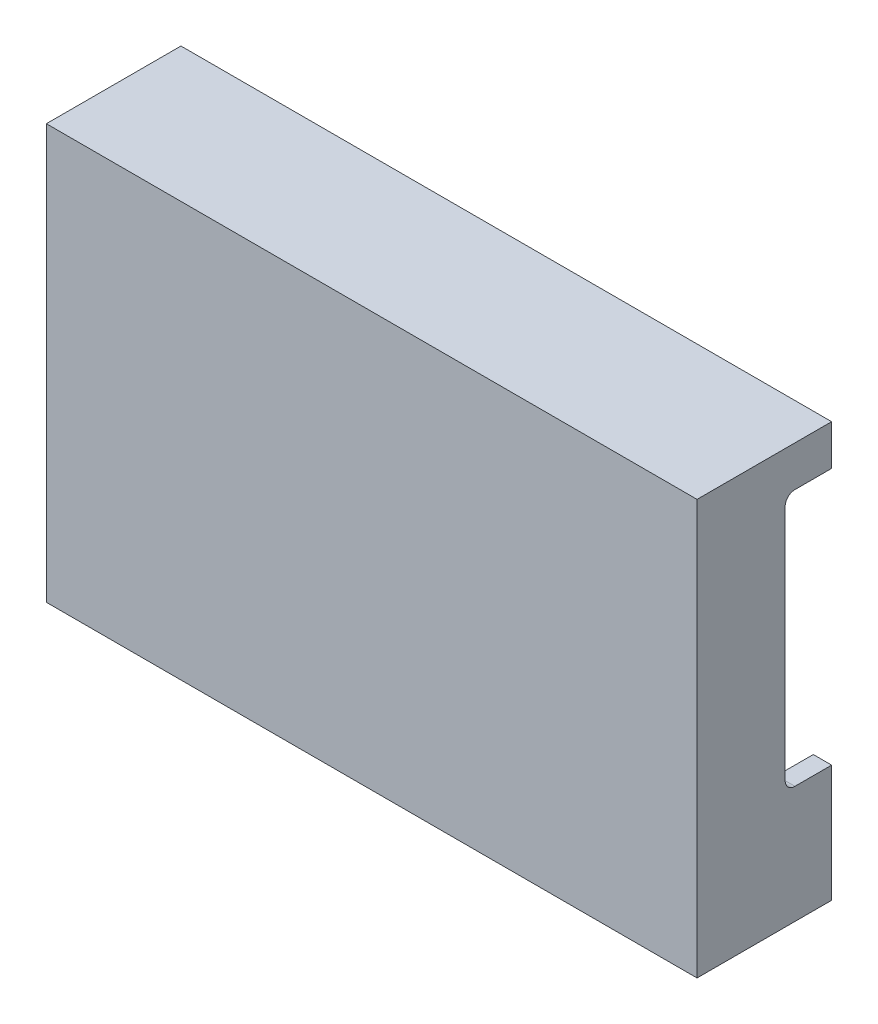
SolidWorks part; units mm, degrees
ref_plane "Спереди" through (0, 0, 0) normal (0, 0, 1) x (1, 0, 0)
ref_plane "Сверху" through (0, 0, 0) normal (0, 1, 0) x (1, 0, 0)
ref_plane "Справа" through (0, 0, 0) normal (1, 0, 0) x (0, 0, -1)
sketch "Эскиз1" plane through (0, 0, 0) normal (0, 0, 1) x (1, 0, 0)
  line L0 (48.984, 29.68) -> (49.984, 29.68)
  line L1 (0, 0) -> (49.784, 0) construction
  line L2 (0, 0) -> (0, 30.48) construction
  line L3 (0, 30.48) -> (49.784, 30.48) construction
  line L4 (49.784, 0) -> (49.784, 30.48) construction
  line L5 (-0.2, -0.2) -> (49.984, -0.2)
  line L6 (-0.2, -0.2) -> (-0.2, 30.68)
  line L7 (-0.2, 30.68) -> (49.984, 30.68)
  line L8 (49.984, -0.2) -> (49.984, 30.68)
  line L9 (0.8, 0.8) -> (48.984, 0.8)
  line L10 (0.8, 0.8) -> (0.8, 29.68)
  line L11 (0.8, 29.68) -> (48.984, 29.68)
  line L12 (48.984, 0.8) -> (48.984, 29.68)
  line L13 (48.984, 6) -> (49.984, 6)
  line L15 (-1.7, -1.7) -> (51.484, -1.7)
  line L16 (-1.7, -1.7) -> (-1.7, 32.18)
  line L17 (-1.7, 32.18) -> (51.484, 32.18)
  line L18 (51.484, -1.7) -> (51.484, 32.18)
  dimension "D1" = 30.48
  dimension "D2" = 49.784
  dimension "D3" = 0.8
  dimension "D4" = 0.8
  dimension "D5" = 0.8
  dimension "D6" = 0.8
  dimension "D7" = 6
  dimension "D8" = 0.2
  dimension "D9" = 0.2
  dimension "D10" = 0.2
  dimension "D11" = 0.2
  dimension "D12" = 1.5
  dimension "D13" = 1.5
  dimension "D14" = 1.5
  dimension "D15" = 1.5
extrude "Бобышка-Вытянуть1" add sketch "Эскиз1" against normal blind 2 contours L9 L12 L11 L10 | L12 L13 L8 L0 region at (24.892, 15.24, 0) region at (49.484, 17.84, 0)
extrude "Бобышка-Вытянуть2" add sketch "Эскиз1<6>" against normal blind 11.4 contours L13 L12 L9 L10 L11 L0 L8 L7 L6 L5 region at (24.892, 30.2692, 0)
sketch "Эскиз1<6>" plane through (0, 0, 0) normal (0, 0, 1) x (1, 0, 0) same geometry as "Эскиз1"
extrude "Бобышка-Вытянуть3" add sketch "Эскиз1<7>" against normal blind 11 contours L15 L18 L17 L16 L8 L5 L6 L7 region at (-1.0694, 15.24, 0)
sketch "Эскиз1<7>" plane through (0, 0, 0) normal (0, 0, 1) x (1, 0, 0) same geometry as "Эскиз1"
sketch "Эскиз2" plane through (49.984, 0, 0) normal (-1, 0, 0) x (0, 0, 1)
  line L0 (-11, 6) -> (-11, 29.68) construction
  line L1 (-11, 28.87) -> (-7.2, 28.87)
  line L2 (-11, 28.87) -> (-11, 7.87)
  line L3 (-11, 7.87) -> (-7.2, 7.87)
  line L4 (-7.2, 28.87) -> (-7.2, 7.87)
  line L5 (-11.4, 6) -> (-2, 6) construction
  point P8 (-11, 18.37)
  dimension "D1" = 21
  dimension "D2" = 12.37
  dimension "D3" = 3.8
extrude "Вырез-Вытянуть1" cut sketch "Эскиз2" against normal through all
sketch "Эскиз3" plane through (0.8, 0, 0) normal (1, 0, 0) x (0, 0, -1)
  line L0 (11.4, 0.8) -> (11.4, 29.68) construction
  line L1 (11.4, 29.5) -> (6.4, 29.5)
  line L2 (11.4, 29.5) -> (11.4, 19.5)
  line L3 (11.4, 19.5) -> (6.4, 19.5)
  line L4 (6.4, 29.5) -> (6.4, 19.5)
  line L6 (11.4, 14.75) -> (2.4, 14.75)
  line L7 (11.4, 14.75) -> (11.4, 1.75)
  line L8 (11.4, 1.75) -> (2.4, 1.75)
  line L9 (2.4, 14.75) -> (2.4, 1.75)
  line L10 (11.4, -0.2) -> (11, -0.2) construction
  point P10 (6.4, 24.5)
  point P15 (2.4, 8.25)
  dimension "D1" = 24.7
  dimension "D2" = 10
  dimension "D3" = 5
  dimension "D4" = 8.45
  dimension "D5" = 13
  dimension "D6" = 9
extrude "Вырез-Вытянуть2" cut sketch "Эскиз3" against normal through all
fillet "Скругление1" radius 0.8 6 edges at (50.734, 7.87, -7.2) (50.734, 28.87, -7.2) (-0.45, 19.5, -6.4) (-0.45, 29.5, -6.4) (-0.45, 1.75, -2.4) (-0.45, 14.75, -2.4)
chamfer "Фаска1" distance 0.4 angle 45 7 edges at (-0.2, 0.775, -11.4) (24.892, -0.2, -11.4) (49.984, 2.9, -11.4) (49.984, 30.18, -11.4) (24.892, 30.68, -11.4) (-0.2, 30.09, -11.4) (-0.2, 17.125, -11.4)
sketch "Эскиз4" plane through (0, 0, -2) normal (0, 0, -1) x (-1, 0, 0)
  line L0 (0.2, -0.2) -> (0.2, 1.75) construction
  line L1 (0.2, -0.2) -> (-49.984, -0.2) construction
  line L2 (-0.8, 29.68) -> (-49.984, 29.68) construction
  line L3 (-35.3, 29.68) -> (-33.3, 29.68)
  line L4 (-35.3, 29.68) -> (-35.3, 21.68)
  line L5 (-35.3, 21.68) -> (-33.3, 21.68)
  line L6 (-33.3, 29.68) -> (-33.3, 21.68)
  circle A0 centre (-11.8, 2.8) radius 2
  circle A1 centre (-27.6, 27.6) radius 2
  circle A2 centre (-40.9, 27.6) radius 2
  point P16 (-34.3, 21.68)
  line M6 (-0.8, 29.68) -> (-49.984, 29.68)
  dimension "D3" = 4
  dimension "D6" = 4
  dimension "D8" = 4
  dimension "D1" = 12
  dimension "D2" = 3
  dimension "D4" = 27.8
  dimension "D5" = 27.8
  dimension "D7" = 41.1
  dimension "D9" = 2
  dimension "D10" = 34.5
  dimension "D11" = 8
extrude "Вырез-Вытянуть3" cut sketch "Эскиз4" against normal blind 1.2 contours A2 | A1 | A0 region at (11.8, 2.8, -2) region at (27.6, 27.6, -2) region at (40.9, 27.6, -2)
extrude "Бобышка-Вытянуть4" add sketch "Эскиз4<3>" along normal blind 8 contours L6 L4 L5 M6 region at (34.3, 25.68, -2)
sketch "Эскиз4<3>" plane through (0, 0, -2) normal (0, 0, -1) x (-1, 0, 0) same geometry as "Эскиз4"
